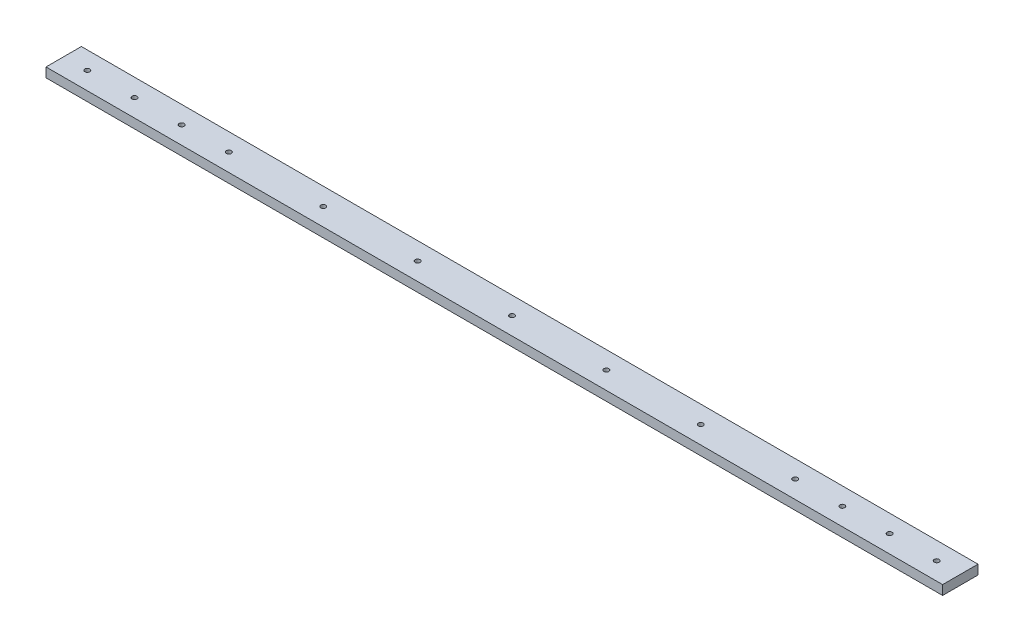
SolidWorks part; units mm, degrees
ref_plane "Front Plane" through (0, 0, 0) normal (0, 0, 1) x (1, 0, 0)
ref_plane "Top Plane" through (0, 0, 0) normal (0, 1, 0) x (1, 0, 0)
ref_plane "Right Plane" through (0, 0, 0) normal (1, 0, 0) x (0, 0, -1)
sketch "Sketch1" plane through (0, 0, 0) normal (0, 1, 0) x (1, 0, 0)
  line L1 (-380, 15) -> (380, 15)
  line L2 (-380, 15) -> (-380, -15)
  line L3 (-380, -15) -> (380, -15)
  line L4 (380, 15) -> (380, -15)
  line L5 (-380, 15) -> (380, -15) construction
  line L6 (-380, -15) -> (380, 15) construction
  point P0 (0, 0)
  dimension "D1" = 760
  dimension "D2" = 30
extrude "Boss-Extrude1" add sketch "Sketch1" along normal blind 8
hole_wizard "M5 Tapped Hole1" positions "Sketch3" profile "Sketch4" tap size "M5" standard "ISO" end condition through all
sketch "Sketch3" plane through (0, 8, 0) normal (0, 1, 0) x (1, 0, 0)
  point P0 (0, 0)
  point P10 (80, 0)
  point P11 (160, 0)
  point P12 (240, 0)
  point P13 (320, 0)
  point P20 (-80, 0)
  point P21 (-160, 0)
  point P22 (-240, 0)
  point P23 (-320, 0)
  dimension "D1" = 5
  dimension "D2" = 5
sketch "Sketch4" plane through (0, 8, 0) normal (1, 0, 0) x (0, 0, 1)
  line L0 (0, 0) -> (0, 8)
  line L1 (0, 8) -> (2.1, 8)
  line L2 (2.1, 8) -> (2.1, 0)
  line L5 (2.1, 0) -> (0, 0)
  line L11 (0, -6.35) -> (0, 107.95) construction
  dimension "Thru Tap Drill Dia." = 4.2
  dimension "Thru Tap Drill Depth" = 8
cosmetic thread "Hole Thread1"
cosmetic thread "Hole Thread2"
cosmetic thread "Hole Thread3"
cosmetic thread "Hole Thread4"
cosmetic thread "Hole Thread5"
cosmetic thread "Hole Thread6"
cosmetic thread "Hole Thread7"
cosmetic thread "Hole Thread8"
cosmetic thread "Hole Thread9"
hole_wizard "M5 Tapped Hole3" positions "Sketch6" profile "Sketch7" tap size "M5" standard "ISO" end condition through all
sketch "Sketch6" plane through (0, 0, 0) normal (0, -1, 0) x (-1, 0, 0)
  line L0 (0, 15) -> (0, -15) construction
  line L1 (-380, 15) -> (380, 15) construction
  line L2 (380, -15) -> (-380, -15) construction
  circle A0 centre (-320, 0) radius 2.1 construction
  point P0 (-280, 0)
  point P2 (-360, 0)
  point P14 (360, 0)
  point P15 (280, 0)
  dimension "D1" = 80
  dimension "D2" = 40
sketch "Sketch7" plane through (280, 0, 0) normal (1, 0, 0) x (0, 0, -1)
  line L0 (0, 0) -> (0, 8)
  line L1 (0, 8) -> (2.1, 8)
  line L2 (2.1, 8) -> (2.1, 0)
  line L5 (2.1, 0) -> (0, 0)
  line L11 (0, -6.35) -> (0, 107.95) construction
  dimension "Thru Tap Drill Dia." = 4.2
  dimension "Thru Tap Drill Depth" = 8
cosmetic thread "Hole Thread11"
cosmetic thread "Hole Thread12"
cosmetic thread "Hole Thread13"
cosmetic thread "Hole Thread14"
